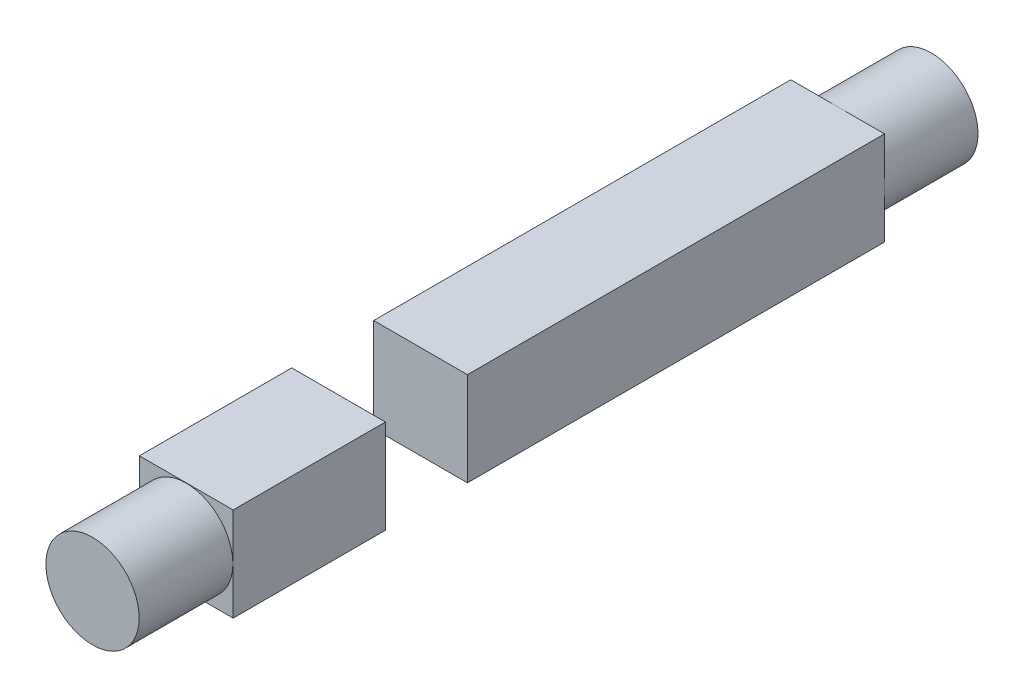
SolidWorks part; units mm, degrees
ref_plane "Front Plane" through (0, 0, 0) normal (0, 0, 1) x (1, 0, 0)
ref_plane "Top Plane" through (0, 0, 0) normal (0, 1, 0) x (1, 0, 0)
ref_plane "Right Plane" through (0, 0, 0) normal (1, 0, 0) x (0, 0, -1)
sketch "Sketch1" plane through (0, 0, 0) normal (0, 0, 1) x (1, 0, 0)
  line L1 (2, -2) -> (-2, -2)
  line L2 (2, -2) -> (2, 2)
  line L3 (2, 2) -> (-2, 2)
  line L4 (-2, -2) -> (-2, 2)
  line L5 (2, -2) -> (-2, 2) construction
  line L6 (2, 2) -> (-2, -2) construction
  dimension "D2" = 4
extrude "Boss-Extrude1" add sketch "Sketch1" along normal mid plane 27.8
sketch "Sketch2" plane through (0, 0, 13.9) normal (0, 0, 1) x (1, 0, 0)
  circle A0 centre (0, 0) radius 1.99
  dimension "D1" = 3.98
extrude "Boss-Extrude2" add sketch "Sketch2" along normal blind 4
mirror "Mirror2" about plane through (0, 0, 0) normal (0, 0, 1) of "Boss-Extrude2"
sketch "Sketch3" plane through (0, 2, 0) normal (0, 1, 0) x (1, 0, 0)
  line L0 (-2, -13.9) -> (-2, 13.9) construction
  line L1 (-2, -7.4) -> (2, -7.4)
  line L2 (-2, -7.4) -> (-2, -3.9)
  line L3 (-2, -3.9) -> (2, -3.9)
  line L4 (2, -7.4) -> (2, -3.9)
  line L5 (2, -13.9) -> (2, 13.9) construction
  line L7 (2, -13.9) -> (-2, -13.9) construction
  dimension "D1" = 3.5
  dimension "D2" = 6.5
extrude "Cut-Extrude1" cut sketch "Sketch3" against normal up to next
